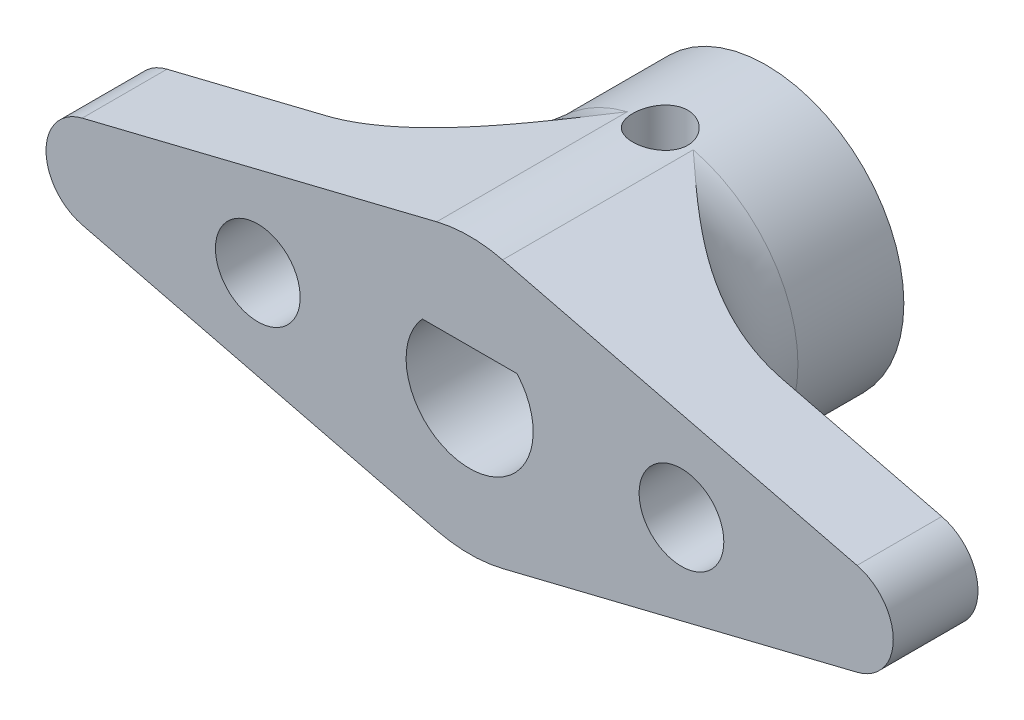
SolidWorks part; units mm, degrees
ref_plane "Front Plane" through (0, 0, 0) normal (0, 0, 1) x (1, 0, 0)
ref_plane "Top Plane" through (0, 0, 0) normal (0, 1, 0) x (1, 0, 0)
ref_plane "Right Plane" through (0, 0, 0) normal (1, 0, 0) x (0, 0, -1)
sketch "Sketch1" plane through (0, 0, 0) normal (0, 0, 1) x (1, 0, 0)
  line L0 (1.5563, 6.3109) -> (18.2887, 2.1846)
  line L1 (0, 0) -> (0, 3.5742) construction
  line L2 (1.5563, -6.3109) -> (18.2887, -2.1846)
  line L3 (2.234, 0) -> (0, 0) construction
  line L4 (-1.5563, -6.3109) -> (-18.2887, -2.1846)
  line L5 (-1.5563, 6.3109) -> (-18.2887, 2.1846)
  line L6 (2.2361, 2) -> (-2.2361, 2)
  arc A0 (-1.5563, -6.3109) -> (1.5563, -6.3109) centre (0, 0) ccw
  arc A1 (18.2887, -2.1846) -> (18.2887, 2.1846) centre (17.75, 0) ccw
  circle A2 centre (10, 0) radius 2
  arc A3 (-18.2887, -2.1846) -> (-18.2887, 2.1846) centre (-17.75, 0) cw
  circle A4 centre (-10, 0) radius 2
  arc A5 (1.5563, 6.3109) -> (-1.5563, 6.3109) centre (0, 0) ccw
  arc A6 (-2.2361, 2) -> (2.2361, 2) centre (0, 0) ccw
  dimension "D1" = 13
  dimension "D2" = 4.5
  dimension "D3" = 4
  dimension "D6" = 6
  dimension "D4" = 17.75
  dimension "D5" = 10
  dimension "D7" = 2
extrude "Boss-Extrude1" add sketch "Sketch1" along normal blind 4
sketch "Sketch3" plane through (0, 0, 0) normal (0, 0, -1) x (-1, 0, 0)
  line L0 (-2.2361, 2) -> (2.2361, 2) construction
  line L1 (-2.2361, 2) -> (2.2361, 2)
  arc A0 (-2.2361, 2) -> (2.2361, 2) centre (0, 0) ccw construction
  arc A1 (-2.2361, 2) -> (2.2361, 2) centre (0, 0) ccw
  circle A2 centre (0, 0) radius 6.5
  dimension "D1" = 13
extrude "Boss-Extrude2" add sketch "Sketch3" along normal blind 10
fillet "Fillet1" radius 5 2 edges at (6.5, 0, 0) (-6.5, 0, 0)
sketch "Sketch4" plane through (0, 2, 0) normal (0, -1, 0) x (1, 0, 0)
  line L0 (-6.5, -10) -> (6.5, -10) construction
  circle A0 centre (0, -5) radius 1.3
  dimension "D1" = 2.6
  dimension "D2" = 5
extrude "Cut-Extrude1" cut sketch "Sketch4" against normal blind 10
